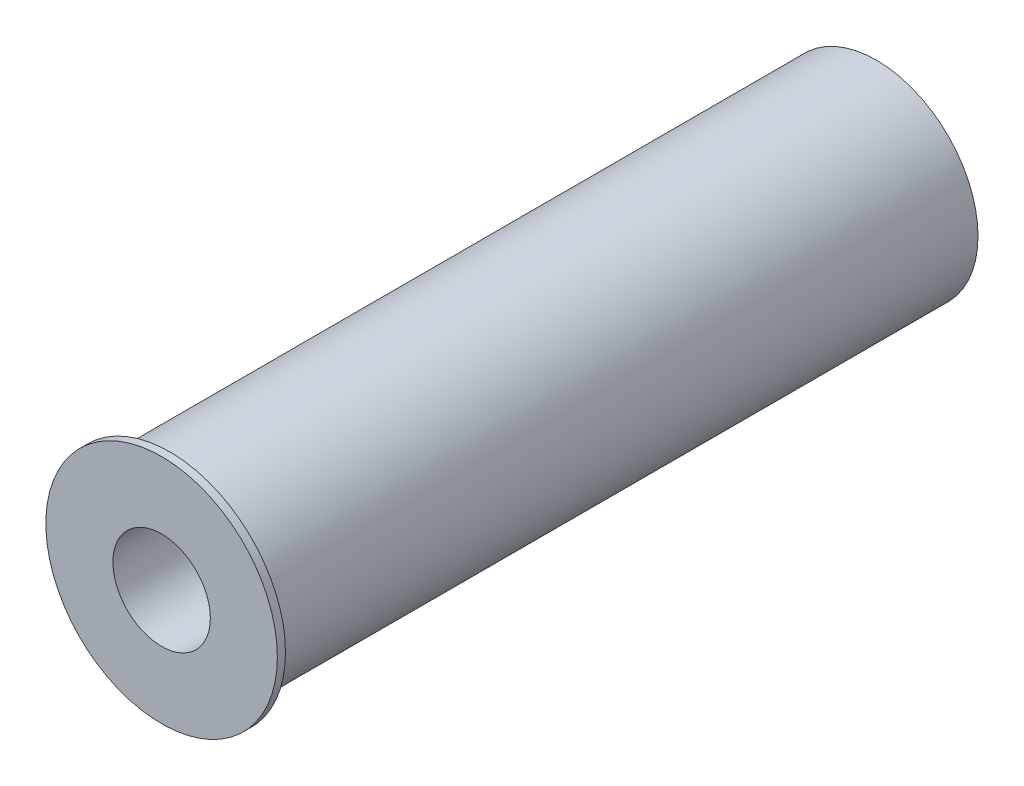
SolidWorks part; units mm, degrees
ref_plane "Ebene vorne" through (0, 0, 0) normal (0, 0, 1) x (1, 0, 0)
ref_plane "Ebene oben" through (0, 0, 0) normal (0, 1, 0) x (1, 0, 0)
ref_plane "Ebene rechts" through (0, 0, 0) normal (1, 0, 0) x (0, 0, -1)
sketch "Skizze1" plane through (0, 0, 0) normal (0, 0, 1) x (1, 0, 0)
  circle A0 centre (0, 0) radius 12.5
  circle A1 centre (0, 0) radius 6
  dimension "D1" = 25
extrude "Aufsatz-Linear austragen1" add sketch "Skizze1" along normal blind 87
sketch "Skizze2" plane through (0, 0, 87) normal (0, 0, 1) x (1, 0, 0)
  circle A0 centre (0, 0) radius 6
  circle A1 centre (0, 0) radius 14.25
  dimension "D1" = 28.5
extrude "Aufsatz-Linear austragen2" add sketch "Skizze2" along normal blind 1
sketch "Skizze3" plane through (0, 0, 0) normal (0, 0, -1) x (-1, 0, 0)
  line L0 (6, 0) -> (12.5, 0) construction
  circle A0 centre (0, 0) radius 6
  circle A1 centre (0, 0) radius 12.5
  circle A2 centre (9.25, 0) radius 1.65
  circle A3 centre (4.625, -8.0107) radius 1.65
  circle A4 centre (-4.625, -8.0107) radius 1.65
  circle A5 centre (-9.25, 0) radius 1.65
  circle A6 centre (-4.625, 8.0107) radius 1.65
  circle A7 centre (4.625, 8.0107) radius 1.65
  point P20 (0, 0)
  dimension "D1" = 6
extrude "Schnitt-Linear austragen1" cut sketch "Skizze3" against normal blind 15 contours A7 | A2 L0 | L0 A2 | A3 | A4 | A5 | A6 region at (-9.25, -0.7003, 0) region at (-9.25, 0.7003, 0) region at (-4.625, -8.0107, 0) region at (4.625, -8.0107, 0) region at (9.25, 0, 0) region at (-4.625, 8.0107, 0)
